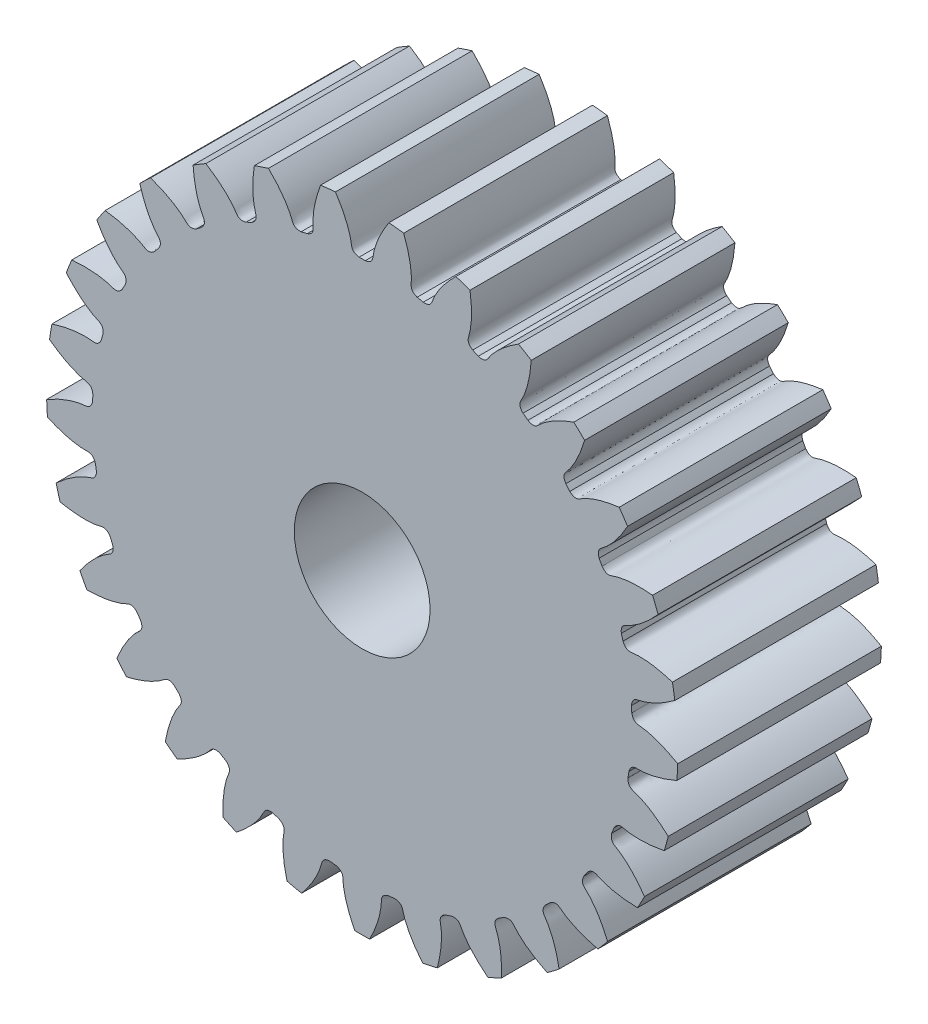
SolidWorks part; units mm, degrees
ref_plane "前视基准面" through (0, 0, 0) normal (0, 0, 1) x (1, 0, 0)
ref_plane "上视基准面" through (0, 0, 0) normal (0, 1, 0) x (1, 0, 0)
ref_plane "右视基准面" through (0, 0, 0) normal (1, 0, 0) x (0, 0, -1)
other "Configuration Table"
sketch "草图1" plane through (0, 0, 0) normal (0, 0, 1) x (1, 0, 0)
  circle A0 centre (0, 0) radius 46.5
extrude "凸台-拉伸1" add sketch "草图1" along normal blind 30
ref_axis "基准轴1" through (0, 0, 30) along (0, 0, -1)
sketch "草图2" plane through (0, 0, 0) normal (0, 0, 1) x (1, 0, 0)
  line L0 (0, 0) -> (0, 46.5) construction
  circle A0 centre (0, 0) radius 46.5 construction
  arc A1 (0.4535, 39.7474) -> (-0.4535, 39.7474) centre (0, 0) ccw
  arc A2 (9.7386, 52.6379) -> (-9.7386, 52.6379) centre (0, 0) ccw
  spline S0 degree 3 poles (0.4535, 39.7474) (1.5698, 39.9136) (1.542, 40.5889) (1.665, 41.2794) (1.6897, 41.4041) (1.7204, 41.5444) (1.7577, 41.6999) (1.8022, 41.8704) (1.8545, 42.0557) (1.9153, 42.2556) (1.9852, 42.4698) (2.0647, 42.698) (2.1544, 42.94) (2.2549, 43.1952) (2.3668, 43.4635) (2.4907, 43.7445) (2.627, 44.0378) (2.7763, 44.343) (2.9392, 44.6596) (3.1162, 44.9874) (3.3077, 45.3258) (3.5143, 45.6743) (3.7364, 46.0325) (3.9746, 46.4) (4.2292, 46.7761) (4.5007, 47.1605) (4.7896, 47.5525) (5.0961, 47.9516) (5.4209, 48.3573) (5.7641, 48.7689) (6.1262, 49.186) (6.5076, 49.6078) (6.9085, 50.0339) (7.3293, 50.4636) (7.7703, 50.8961) (8.2317, 51.3311) (8.8827, 51.9205) (9.3904, 52.3529) (9.7386, 52.6379) knots 0 0 0 0 0.115495 0.122355 0.130227 0.139111 0.149007 0.159915 0.171835 0.184766 0.19871 0.213666 0.229634 0.246613 0.264605 0.283609 0.303625 0.324652 0.346692 0.369743 0.393807 0.418883 0.44497 0.47207 0.500181 0.529305 0.55944 0.590587 0.622747 0.655918 0.690102 0.725297 0.761504 0.798724 0.836955 0.876198 0.916454 1 1 1 1
  spline S1 degree 3 poles (-0.4535, 39.7474) (-1.5698, 39.9136) (-1.542, 40.5889) (-1.665, 41.2794) (-1.6897, 41.4041) (-1.7204, 41.5444) (-1.7577, 41.6999) (-1.8022, 41.8704) (-1.8545, 42.0557) (-1.9153, 42.2556) (-1.9852, 42.4698) (-2.0647, 42.698) (-2.1544, 42.94) (-2.2549, 43.1952) (-2.3668, 43.4635) (-2.4907, 43.7445) (-2.627, 44.0378) (-2.7763, 44.343) (-2.9392, 44.6596) (-3.1162, 44.9874) (-3.3077, 45.3258) (-3.5143, 45.6743) (-3.7364, 46.0325) (-3.9746, 46.4) (-4.2292, 46.7761) (-4.5007, 47.1605) (-4.7896, 47.5525) (-5.0961, 47.9516) (-5.4209, 48.3573) (-5.7641, 48.7689) (-6.1262, 49.186) (-6.5076, 49.6078) (-6.9085, 50.0339) (-7.3293, 50.4636) (-7.7703, 50.8961) (-8.2317, 51.3311) (-8.8827, 51.9205) (-9.3904, 52.3529) (-9.7386, 52.6379) knots 0 0 0 0 0.115495 0.122355 0.130227 0.139111 0.149007 0.159915 0.171835 0.184766 0.19871 0.213666 0.229634 0.246613 0.264605 0.283609 0.303625 0.324652 0.346692 0.369743 0.393807 0.418883 0.44497 0.47207 0.500181 0.529305 0.55944 0.590587 0.622747 0.655918 0.690102 0.725297 0.761504 0.798724 0.836955 0.876198 0.916454 1 1 1 1
extrude "切除-拉伸1" cut sketch "草图2" along normal through all
pattern_circular "阵列(圆周)1" count 29 every 12.414 about axis through (0, 0, 30) along (0, 0, -1) of "切除-拉伸1"
sketch "草图3" plane through (0, 0, 0) normal (0, 0, 1) x (1, 0, 0)
  circle A0 centre (0, 0) radius 43.5 construction
  dimension "Dn" = 87
sketch "草图4" plane through (0, 0, 0) normal (0, 0, -1) x (-1, 0, 0)
  circle A0 centre (0, 0) radius 10
  dimension "D1" = 20
extrude "切除-拉伸2" cut sketch "草图4" against normal blind 300
